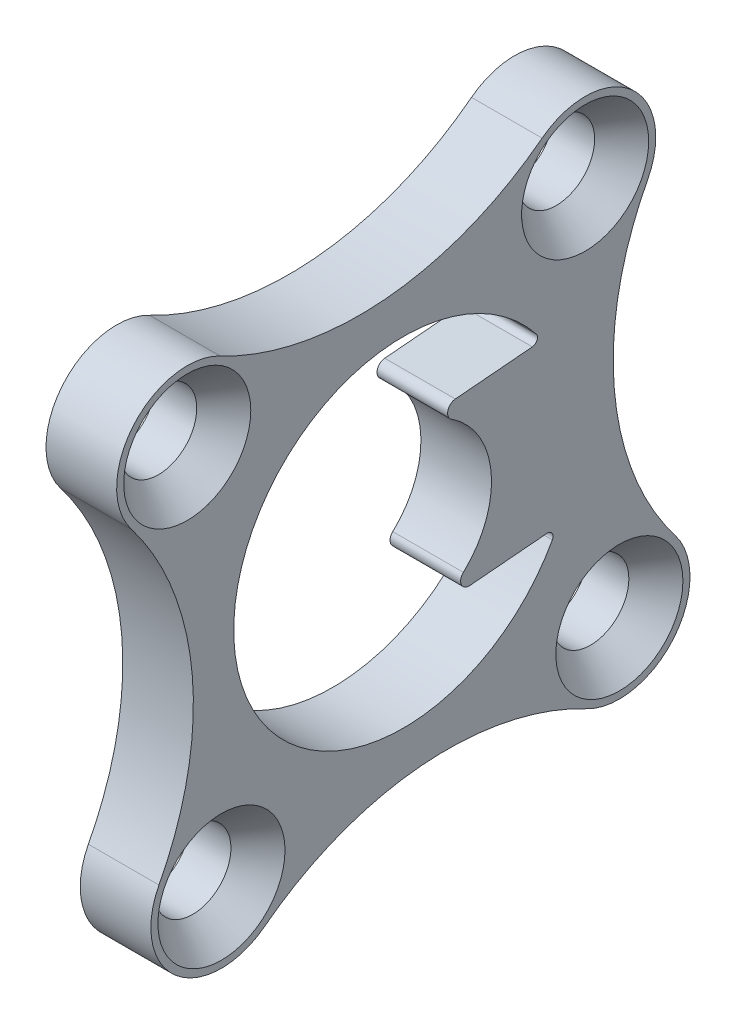
SolidWorks part; units mm, degrees
material "6061-T6 (SS)"
ref_plane "Front Plane" through (0, 0, 0) normal (0, 0, 1) x (1, 0, 0)
ref_plane "Top Plane" through (0, 0, 0) normal (0, 1, 0) x (1, 0, 0)
ref_plane "Right Plane" through (0, 0, 0) normal (1, 0, 0) x (0, 0, -1)
sketch "Sketch1" plane through (-42.315, 0, 0) normal (-1, 0, 0) x (0, 0, 1)
  line L0 (-5.8027, 4.3231) -> (-2.3399, 4.0253)
  line L1 (-7.4878, 4.468) -> (-5.6505, 4.31) construction
  line L2 (-2.9929, -3.5667) -> (-6.4557, -3.2689)
  line L3 (-8.1407, -3.1239) -> (-3.1735, -3.5511) construction
  line L5 (-5.6505, 4.31) -> (-0.7807, 3.8912) construction
  line L6 (9.7167, 8.1777) -> (-9.7167, -8.1777) construction
  line L7 (8.1777, -9.7167) -> (-8.1777, 9.7167) construction
  arc A0 (-2.3399, 4.0253) -> (-2.1648, 3.3264) centre (-2.3726, 3.6457) cw
  arc A1 (-2.1648, 3.3264) -> (-2.7009, -2.9079) centre (0, 0) ccw
  arc A2 (-2.7009, -2.9079) -> (-2.9929, -3.5667) centre (-2.9602, -3.1871) cw
  circle A3 centre (0, 0) radius 3.9687 construction
  circle A4 centre (0, 0) radius 3.9687 construction
  arc A5 (-5.8027, 4.3231) -> (-5.9801, 4.7338) centre (-5.781, 4.5762) cw
  arc A8 (-5.9801, 4.7338) -> (-6.7006, -3.6433) centre (0, 0) cw
  arc A9 (-6.7006, -3.6433) -> (-6.4557, -3.2689) centre (-6.4774, -3.5219) cw
  circle A10 centre (0, 0) radius 15.875
  arc A11 (-6.5469, -3.6589) -> (-5.8261, 4.723) centre (0, 0) ccw construction
  circle A12 centre (-8.1777, 9.7167) radius 3.175 construction
  circle A13 centre (-8.1777, 9.7167) radius 2.6924 construction
  circle A14 centre (0, 0) radius 9.525 construction
  dimension "D1" = 0.381
  dimension "D2" = 0.254
  dimension "D3" = 25.4
  dimension "D4" = 0.127
  dimension "D6" = 5.3848
  dimension "D7" = 19.05
  dimension "D5" = 45
extrude "Boss-Extrude1" add sketch "Sketch1" against normal blind 3.175
sketch "Sketch2" plane through (-42.315, 0, 0) normal (-1, 0, 0) x (0, 0, 1)
  line L0 (8.1777, -9.7167) -> (-8.1777, 9.7167) construction
  line L1 (-5.8027, 4.3231) -> (-2.3399, 4.0253) construction
  line L2 (0.8162, 9.49) -> (1.3603, 15.8166)
  arc A0 (-10.2222, 12.1459) -> (1.3603, 15.8166) centre (0, 0) cw
  circle A1 centre (0, 0) radius 15.875 construction
  circle A3 centre (0, 0) radius 9.525 construction
  arc A5 (-6.2421, 12.2334) -> (-10.2222, 12.1459) centre (-8.1777, 9.7167) ccw
  circle A6 centre (-8.1777, 9.7167) radius 3.175 construction
  arc A7 (-6.2421, 12.2334) -> (0.8162, 9.49) centre (1.9704, 22.9108) ccw
extrude "Cut-Extrude1" cut sketch "Sketch2" against normal through all
mirror "Mirror1" about plane through (-39.14, 9.49, 0.8162) normal (0, -0.0857, 0.9963) of "Cut-Extrude1"
pattern_circular "CirPattern2" count 4 over 360 about axis through (-42.315, 0, 0) along (-1, 0, 0) of "Cut-Extrude1", "Mirror1"
hole_wizard "CSK for #4 Flat Head Machine Screw1" positions "Sketch3" profile "Sketch4" countersink size "#4" standard "ANSI Inch" end condition up to next
sketch "Sketch3" plane through (-39.14, 0, 0) normal (1, 0, 0) x (0, 0, -1)
  point P0 (9.7167, -8.1777)
  point P3 (9.7167, -8.1777)
  point P6 (9.7167, -8.1777)
  point P9 (9.7167, -8.1777)
  point P13 (8.1777, 9.7167)
  point P16 (-9.7167, 8.1777)
  point P19 (-8.1777, -9.7167)
sketch "Sketch4" plane through (-39.14, -8.1777, -9.7167) normal (0, 1, 0) x (0, 0, -1)
  line L0 (0, 0) -> (0, 3.175)
  line L1 (0, 3.175) -> (1.7272, 3.175)
  line L2 (1.7272, 3.175) -> (1.7272, 1.3003)
  line L3 (1.7272, 1.3003) -> (2.8575, 0)
  line L5 (2.8575, 0) -> (0, 0)
  line L6 (-1.7272, 1.3003) -> (-2.8575, 0) construction
  line L11 (0, -6.35) -> (0, 107.95) construction
  dimension "Thru Hole Dia." = 3.4544
  dimension "Thru Hole Depth" = 3.175
  dimension "Near C'Sink Dia." = 5.715
  dimension "Near C'Sink Angle" = 82
